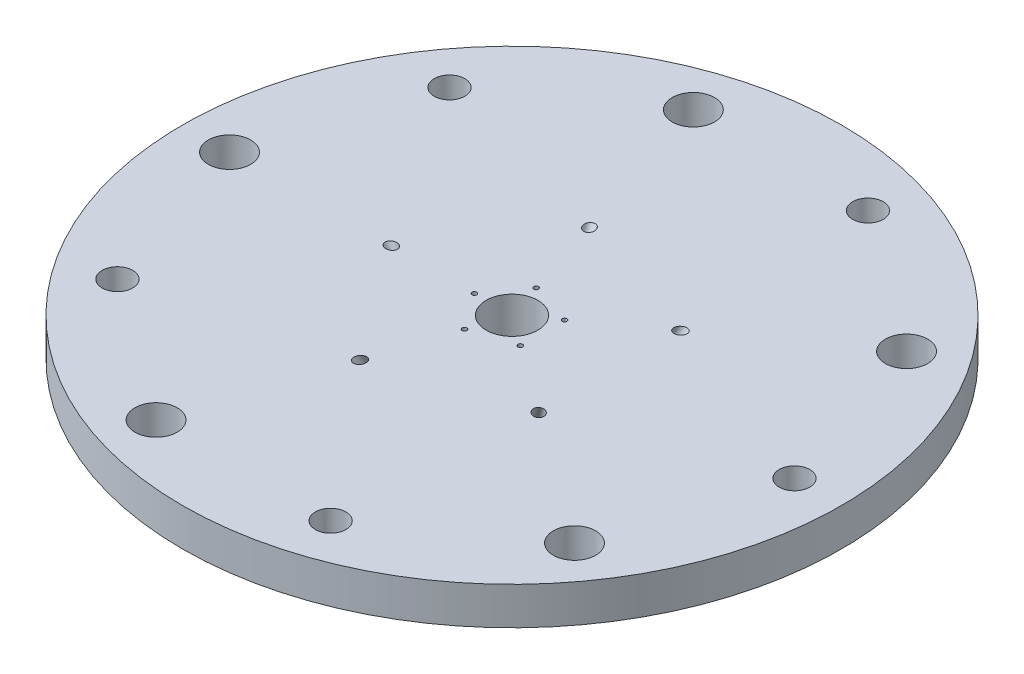
SolidWorks part; units mm, degrees
other "Markup1"
sketch "Sketch22" plane through (67.4, 16.5, 67.4) normal (0.6133, 0.6241, 0.4841) x (0.6587, -0.0661, -0.7495)
sketch "Sketch37" plane through (67.4, 28, 67.4) normal (0.6133, 0.6241, 0.4841) x (0.6587, -0.0661, -0.7495)
other "Markup2"
sketch "Sketch23" plane through (67.4, 26.5, 67.4) normal (0.1362, 0.0894, 0.9866) x (0.9893, -0.0646, -0.1307)
sketch "Sketch38" plane through (67.4, 28, 67.4) normal (0.1362, 0.0894, 0.9866) x (0.9893, -0.0646, -0.1307)
other "Markup5"
sketch "Sketch28" plane through (-67.4, 30.5, 67.4) normal (-0.0176, 0.5562, 0.8308) x (0.9998, 0.0146, 0.0115)
sketch "Sketch39" plane through (-67.4, 28, 67.4) normal (-0.0176, 0.5562, 0.8308) x (0.9998, 0.0146, 0.0115)
material "1023 Carbon Steel Sheet (SS)"
ref_plane "Front Plane" through (0, 0, 0) normal (0, 0, 1) x (1, 0, 0)
ref_plane "Top Plane" through (0, 0, 0) normal (0, 1, 0) x (1, 0, 0)
ref_plane "Right Plane" through (0, 0, 0) normal (1, 0, 0) x (0, 0, -1)
sketch "Sketch1" plane through (0, 0, 0) normal (0, 0, 1) x (1, 0, 0)
  line L5 (-47.4, 0) -> (-47.4, -8)
  line L9 (-7, -8) -> (0, -8)
  line L10 (0, -8) -> (0, 0)
  line L12 (-7, -8) -> (-17.4, -8)
  line L24 (-17.4, -8) -> (-47.4, -8)
  line L25 (-47.4, 0) -> (0, 0)
  dimension "D2" = 8
  dimension "D3" = 47.4
  dimension "D8" = 0
  dimension "D10" = 7
revolve "Revolve1" add sketch "Sketch1" angle 360 about L10
sketch "Sketch4" plane through (0, 0, 0) normal (0, 0, 1) x (1, 0, 0)
  line L0 (0, 0) -> (0, 13.3666) construction
sketch "Sketch2" plane through (0, 0, 0) normal (0, 1, 0) x (1, 0, 0)
  circle A0 centre (-8, 0) radius 0.5
  dimension "D2" = 1
  dimension "D1" = 8
extrude "Fuel holes" cut sketch "Sketch2" against normal up to next from offset 5
pattern_circular "CirPattern1" count 5 over 360 about axis through (0, 0, 0) along (0, 1, 0) of "Fuel holes" reverse direction yes
sketch "Sketch5" plane through (0, 0, 0) normal (1, 0, 0) x (0, 0, -1)
sketch "Sketch19" plane through (0, -8, 0) normal (0, -1, 0) x (1, 0, 0)
  line L0 (-47.4, 0) -> (-70, 0) construction
  line L1 (-56.6312, -41.145) -> (0, 0) construction
  circle A1 centre (0, 0) radius 47.4
  circle A2 centre (0, 0) radius 70
  circle A3 centre (-60, 0) radius 4.5
  circle A4 centre (0, 0) radius 47.4 construction
  circle A5 centre (-48.541, -35.2671) radius 3.25
  point P11 (0, 0)
  dimension "D2" = 9
  dimension "D5" = 6.5
  dimension "D3" = 60
  dimension "D4" = 36
  dimension "D6" = 60
  dimension "D1" = 22.6
extrude "Boss-Extrude2" add sketch "Sketch19" against normal blind 8 contours A1 | A2
extrude "Bolt holes" cut sketch "Sketch19<3>" against normal up to surface (8 mm away) contours A3 | A5 up to face at (-1.9721, 0, -7.6085)
sketch "Sketch19<3>" plane through (0, -8, 0) normal (0, -1, 0) x (1, 0, 0) same geometry as "Sketch19"
sketch "Sketch21" plane through (0, 0, 0) normal (0, 0, 1) x (1, 0, 0)
  line L0 (0, 0) -> (51.8972, 0) construction
  line L1 (0, 0) -> (0, -5.4672) construction
sketch "Sketch8" plane through (-29.8564, -8, 0) normal (0, -1, 0) x (-1, 0, 0)
  line L0 (-29.8564, 0) -> (-8.8564, 0) construction
  line L1 (-8.8564, 0) -> (-8.8564, 32.0516) construction
  circle A2 centre (-8.8564, 0) radius 1.75
  dimension "D1" = 3.5
  dimension "D2" = 21
ref_plane "Plane1" through (-21, 0, 0) normal (1, 0, 0) x (0, 0, -1)
ref_plane "Plane2" through (-1.7859, 3.0933, 0) normal (0.5, -0.866, 0) x (0, 0, -1)
sketch "Sketch41" plane through (-1.7859, 3.0933, 0) normal (0.5, -0.866, 0) x (0, 0, -1)
  circle A0 centre (0, -22.1865) radius 1.15
  dimension "D1" = 2.3
extrude "Cut-Extrude7" cut sketch "Sketch41" against normal blind 10 and the other way through all
sketch "Sketch31" plane through (0, -8, 0) normal (0, -1, 0) x (1, 0, 0)
  circle A0 centre (0, 0) radius 27.4
  dimension "D1" = 54.8
sketch "Sketch32" plane through (0, 0, 0) normal (0, 1, 0) x (1, 0, 0)
  circle A0 centre (0, 0) radius 5.5
  dimension "D1" = 11
extrude "Cut-Extrude3" cut sketch "Sketch32" against normal up to next contours A0
sketch "Sketch35" plane through (0, 0, 0) normal (0, 0, 1) x (1, 0, 0)
  line L0 (0, 0) -> (0, 22.3821) construction
pattern_circular "CirPattern9" count 5 over 360 about axis through (0, 0, 0) along (0, 1, 0) of "Cut-Extrude7"
pattern_circular "CirPattern10" count 5 over 360 about axis through (0, 0, 0) along (0, 1, 0) of "Bolt holes"
equation "\"Bolts\"= 10"
equation "\"D4@Sketch19\"=360/\"Bolts\""
